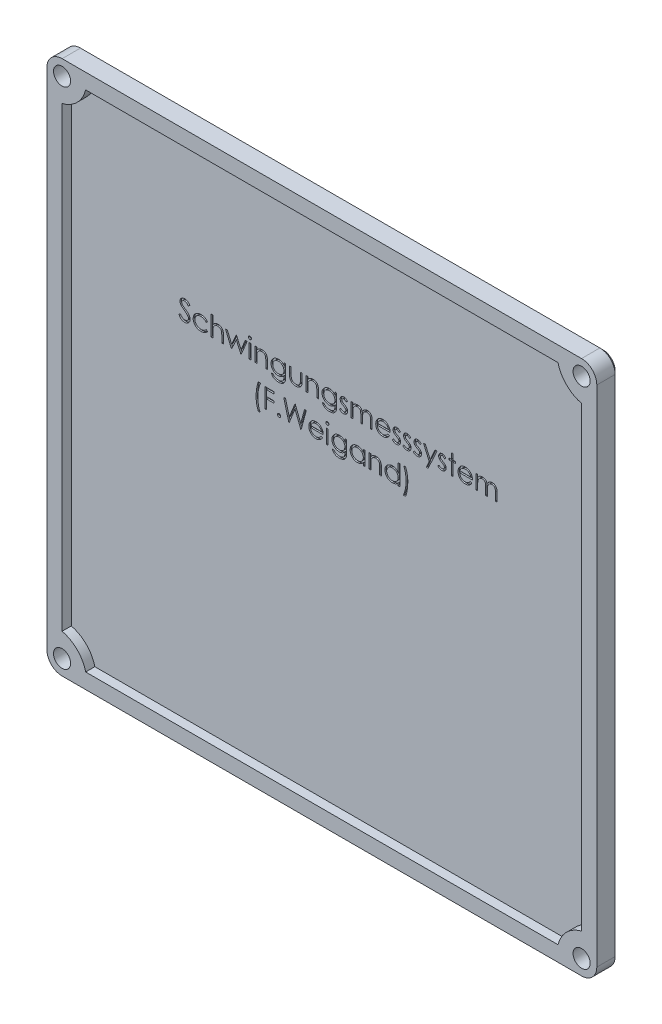
SolidWorks part; units mm, degrees
note: The reader was unsure of these and kept them because the rebuilt part matched: shared geometry of "Skizze1<2>", "Skizze2<5>".
ref_plane "Ebene vorne" through (0, 0, 0) normal (0, 0, 1) x (1, 0, 0)
ref_plane "Ebene oben" through (0, 0, 0) normal (0, 1, 0) x (1, 0, 0)
ref_plane "Ebene rechts" through (0, 0, 0) normal (1, 0, 0) x (0, 0, -1)
sketch "Skizze1" plane through (0, 0, 0) normal (0, 0, 1) x (1, 0, 0)
  line L1 (85, -82.5) -> (-85, -82.5)
  line L2 (85, -82.5) -> (85, 82.5)
  line L3 (85, 82.5) -> (-85, 82.5)
  line L4 (-85, -82.5) -> (-85, 82.5)
  line L5 (85, -82.5) -> (-85, 82.5) construction
  line L6 (85, 82.5) -> (-85, -82.5) construction
  line L7 (90, -87.5) -> (-90, -87.5)
  line L8 (90, -87.5) -> (90, 87.5)
  line L9 (90, 87.5) -> (-90, 87.5)
  line L10 (-90, -87.5) -> (-90, 87.5)
  line L11 (90, -87.5) -> (-90, 87.5) construction
  line L12 (90, 87.5) -> (-90, -87.5) construction
  point P0 (0, 0)
  point P5 (0, 0)
  dimension "D1" = 5
  dimension "D2" = 5
  dimension "D3" = 180
  dimension "D4" = 175
extrude "Aufsatz-Linear austragen1" add sketch "Skizze1" along normal blind 3
extrude "Aufsatz-Linear austragen2" add sketch "Skizze1<2>" against normal blind 4 contours L9 L10 L7 L8
sketch "Skizze1<2>" plane through (0, 0, 0) normal (0, 0, 1) x (1, 0, 0) same geometry as "Skizze1"
sketch "Skizze2" plane through (0, 0, 3) normal (0, 0, 1) x (1, 0, 0)
  line L0 (-87.5, 85) -> (-87.5, 74.5)
  line L1 (-87.5, 85) -> (-77, 85)
  line L2 (-87.5, 85) -> (-80.0754, 77.5754) construction
  line L3 (-90, 87.5) -> (-85, 82.5) construction
  line L4 (0, 9.9788) -> (0, -13.3423) construction
  line L5 (-10.3406, 0) -> (19.0775, 0) construction
  line L6 (87.5, 85) -> (87.5, 74.5)
  line L7 (87.5, 85) -> (77, 85)
  line L8 (87.5, -85) -> (77, -85)
  line L9 (87.5, -85) -> (87.5, -74.5)
  line L10 (-87.5, -85) -> (-87.5, -74.5)
  line L11 (-87.5, -85) -> (-77, -85)
  arc A0 (-87.5, 74.5) -> (-77, 85) centre (-87.5, 85) ccw
  circle A1 centre (-85.0251, 82.5251) radius 2.8
  arc A2 (87.5, 74.5) -> (77, 85) centre (87.5, 85) cw
  circle A3 centre (85.0251, 82.5251) radius 2.8
  arc A4 (87.5, -74.5) -> (77, -85) centre (87.5, -85) ccw
  circle A5 centre (85.0251, -82.5251) radius 2.8
  circle A6 centre (-85.0251, -82.5251) radius 2.8
  arc A7 (-87.5, -74.5) -> (-77, -85) centre (-87.5, -85) cw
  dimension "D1" = 7
  dimension "D2" = 10.5
  dimension "D3" = 5.6
extrude "Schnitt-Linear austragen2" cut sketch "Skizze2" against normal through all contours A1 | A3 | A5 | A6
fillet "Verrundung1" radius 5 4 edges at (-90, -87.5, -0.5) (90, -87.5, -0.5) (90, 87.5, -0.5) (-90, 87.5, -0.5)
chamfer "Fase1" distance 1 angle 45 8 edges at (88.5355, -86.0355, -4) (90, 0, -4) (88.5355, 86.0355, -4) (0, 87.5, -4) (-88.5355, 86.0355, -4) (-90, 0, -4) (-88.5355, -86.0355, -4) (0, -87.5, -4)
extrude "Aufsatz-Linear austragen3" add sketch "Skizze2<5>" against normal up to surface (3 mm away)
sketch "Skizze2<5>" plane through (0, 0, 3) normal (0, 0, 1) x (1, 0, 0) same geometry as "Skizze2"
sketch "Skizze3" plane through (0, 0, 0) normal (0, 0, 1) x (1, 0, 0)
  text T0 "Schwingungsmesssystem\r\n          (F.Weigand)" font "Century Gothic" height in points 24
  dimension "D1" = 50
  dimension "D2" = 30
extrude "Schnitt-Linear austragen3" cut sketch "Skizze3" against normal blind 0.5
equation "\"D2@Skizze1\"=\"D1@Skizze1\""
